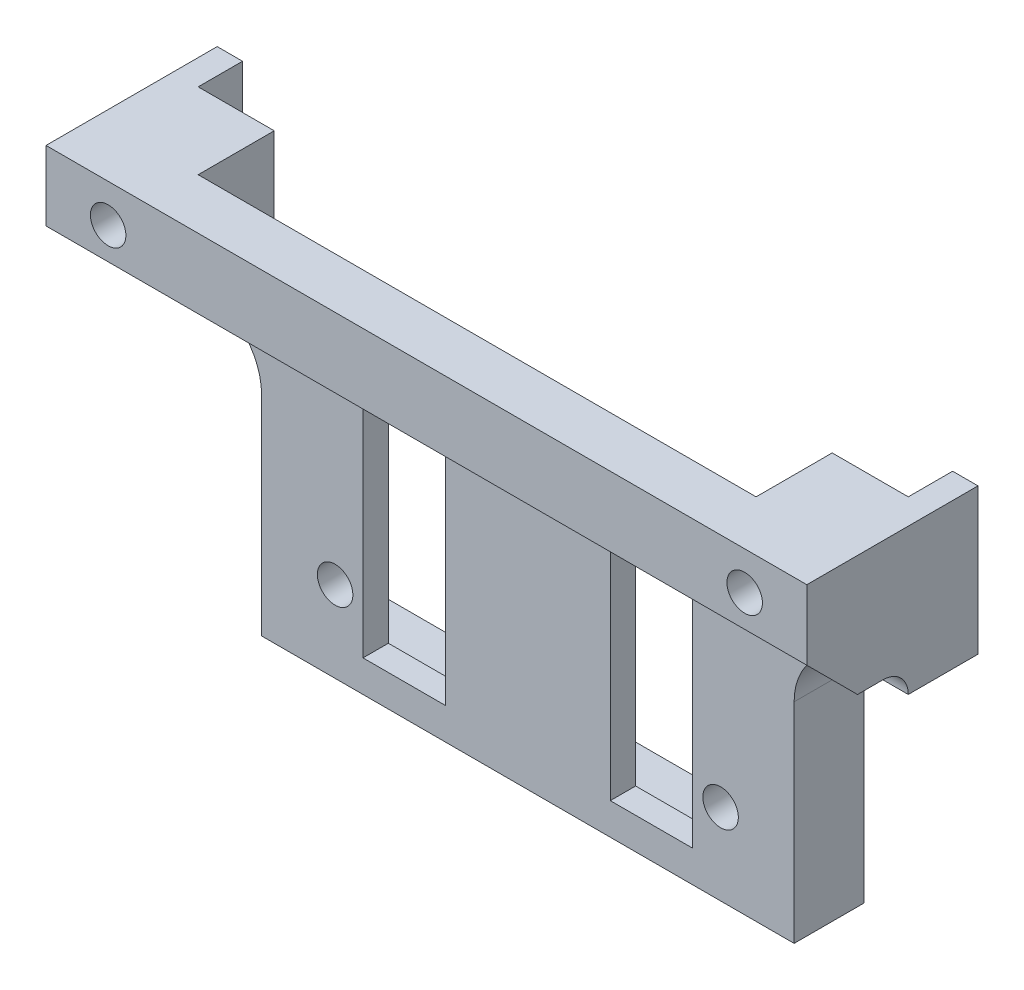
SolidWorks part; units mm, degrees
ref_plane "前视基准面" through (0, 0, 0) normal (0, 0, 1) x (1, 0, 0)
ref_plane "上视基准面" through (0, 0, 0) normal (0, 1, 0) x (1, 0, 0)
ref_plane "右视基准面" through (0, 0, 0) normal (1, 0, 0) x (0, 0, -1)
sketch "草图1" plane through (0, 0, 0) normal (0, 0, 1) x (1, 0, 0)
  line L1 (-21, 17.5) -> (21, 17.5)
  line L2 (-21, 17.5) -> (-21, -17.5)
  line L3 (-21, -17.5) -> (21, -17.5)
  line L4 (21, 17.5) -> (21, -17.5)
  line L5 (0, -17.5) -> (0, 17.5) construction
  line L6 (-21, 0) -> (21, 0) construction
  point P0 (0, 0)
  dimension "D1" = 35
  dimension "D2" = 42
extrude "凸台-拉伸1" add sketch "草图1" along normal blind 10
sketch "草图2" plane through (0, 0, 10) normal (0, 0, 1) x (1, 0, 0)
  line L0 (0, 11.512) -> (0, -11.1488) construction
  line L1 (-21, -17.5) -> (21, -17.5) construction
  line L2 (-13, 8) -> (-6.5, 8)
  line L3 (-13, 8) -> (-13, -13)
  line L4 (-13, -13) -> (-6.5, -13)
  line L5 (-6.5, 8) -> (-6.5, -13)
  line L6 (6.5, 8) -> (6.5, -13)
  line L7 (13, -13) -> (6.5, -13)
  line L8 (13, 8) -> (13, -13)
  line L9 (13, 8) -> (6.5, 8)
  dimension "D1" = 13
  dimension "D2" = 26
  dimension "D3" = 4.5
  dimension "D4" = 21
extrude "切除-拉伸1" cut sketch "草图2" against normal blind 10
sketch "草图5" plane through (0, 0, 0) normal (0, 0, -1) x (-1, 0, 0)
  line L0 (-21, 17.5) -> (21, 17.5) construction
  line L1 (-21, 17.5) -> (-30, 17.5)
  line L2 (-21, 17.5) -> (-21, 6)
  line L3 (-21, 6) -> (-30, 6)
  line L4 (-30, 17.5) -> (-30, 6)
  line L5 (-21, -17.5) -> (-21, 17.5) construction
  line L6 (0, 25.3012) -> (0, -3.3354) construction
  line L7 (30, 17.5) -> (30, 6)
  line L8 (21, 6) -> (30, 6)
  line L9 (21, 17.5) -> (21, 6)
  line L10 (21, 17.5) -> (30, 17.5)
  dimension "D1" = 11.5
  dimension "D2" = 9
extrude "凸台-拉伸2" add sketch "草图5" against normal up to surface (10 mm away) up to face at (9.75, -2.5, 10)
sketch "草图6" plane through (0, 0, 0) normal (0, 0, -1) x (-1, 0, 0)
  circle A0 centre (-25.1, 14.5) radius 1.4 construction
  circle A1 centre (25.1, 14.5) radius 1.4 construction
  circle A2 centre (-25.1, 14.5) radius 1.4
  circle A3 centre (25.1, 14.5) radius 1.4
  circle A4 centre (15.2, -9.1) radius 1.4 construction
  circle A5 centre (-15.2, -9.1) radius 1.4 construction
  circle A6 centre (-15.2, -9.1) radius 1.4
  circle A7 centre (15.2, -9.1) radius 1.4
extrude "切除-拉伸4" cut sketch "草图6" against normal blind 10
sketch "草图3" plane through (0, 0, 0) normal (0, 0, -1) x (-1, 0, 0)
  line L1 (-30, 17.5) -> (30, 17.5) construction
  line L2 (22, 9.5) -> (-22, 9.5)
  line L3 (22, 9.5) -> (22, 17.5)
  line L4 (22, 17.5) -> (-22, 17.5)
  line L5 (-22, 9.5) -> (-22, 17.5)
  line L6 (0, 17.5) -> (0, 9.5) construction
  line L7 (22, 13.5) -> (-22, 13.5) construction
  point P0 (0, 13.5)
  dimension "D1" = 44
  dimension "D2" = 8
extrude "切除-拉伸2" cut sketch "草图3" against normal blind 6
sketch "草图8" plane through (0, 0, 10) normal (0, 0, 1) x (1, 0, 0)
  line L0 (-26.679, -15.5) -> (32.738, -15.5)
  line L1 (-21, -17.5) -> (21, -17.5) construction
  dimension "D1" = 2
extrude "切除-拉伸-薄壁1" cut sketch "草图8" against normal blind 10 and the other way through all thin
sketch "草图10" plane through (0, 0, 0) normal (0, 0, -1) x (-1, 0, 0)
  line L0 (-30, 17.5) -> (-28, 17.5)
  line L1 (-30, 17.5) -> (-22, 17.5) construction
  line L2 (-28, 17.5) -> (-28, 7)
  line L3 (-28, 7) -> (-19, 7)
  line L4 (-19, 7) -> (-19, -13.5)
  line L5 (-19, -13.5) -> (19, -13.5)
  line L6 (0, 4.8955) -> (0, -18.7545) construction
  line L7 (30, 6) -> (21, 6)
  line L8 (30, 17.5) -> (30, 6)
  line L9 (21, 6) -> (21, -15.5)
  line L10 (19, 7) -> (19, -13.5)
  line L11 (28, 7) -> (19, 7)
  line L12 (-21, 6) -> (-21, -15.5)
  line L13 (-21, -15.5) -> (21, -15.5)
  line L14 (21, -15.5) -> (21, 6)
  line L15 (21, 6) -> (30, 6)
  line L16 (30, 6) -> (30, 17.5)
  line L17 (30, 17.5) -> (22, 17.5)
  line L18 (22, 17.5) -> (22, 9.5)
  line L19 (22, 9.5) -> (-22, 9.5)
  line L20 (-22, 9.5) -> (-22, 17.5)
  line L21 (-22, 17.5) -> (-30, 17.5)
  line L22 (-30, 17.5) -> (-30, 6)
  line L23 (-30, 6) -> (-21, 6)
  line L24 (-21, 6) -> (-21, -15.5)
  line L25 (-21, -15.5) -> (21, -15.5)
  line L26 (21, -15.5) -> (21, 6)
  line L27 (21, 6) -> (30, 6)
  line L28 (30, 6) -> (30, 17.5)
  line L29 (28, 17.5) -> (28, 7)
  line L30 (30, 17.5) -> (28, 17.5)
  line L34 (-30, 17.5) -> (-30, 6)
  line L35 (-30, 6) -> (-21, 6)
  point P22 (-25.5, 6)
  point P24 (0, -13.5)
  line M26 (-21, 6) -> (-21, -15.5)
  line M27 (-21, -15.5) -> (21, -15.5)
  line M28 (21, -15.5) -> (21, 6)
  line M29 (21, 6) -> (30, 6)
  line M30 (30, 6) -> (30, 17.5)
  line M31 (30, 17.5) -> (22, 17.5)
  line M35 (-22, 17.5) -> (-30, 17.5)
  line M36 (-30, 17.5) -> (-30, 6)
  line M37 (-30, 6) -> (-21, 6)
  dimension "D2" = 2
  dimension "D3" = 2
  dimension "D4" = 1
  dimension "D5" = 2
  dimension "D1" = 0
extrude "凸台-拉伸3" add sketch "草图10" along normal blind 3.5 contours L6 L5 L4 L3 L2 M35 M36 M37 M26 M27 | L5 L6 L25 L29 L11 L10 M28 M29 M30 M31
sketch "草图11" plane through (0, 0, 10) normal (0, 0, 1) x (1, 0, 0)
  circle A0 centre (25.1, 14.5) radius 1.4 construction
  circle A1 centre (-25.1, 14.5) radius 1.4 construction
  circle A2 centre (-15.2, -9.1) radius 1.4 construction
  circle A3 centre (25.1, 14.5) radius 1.4
  circle A4 centre (-25.1, 14.5) radius 1.4
  circle A5 centre (-15.2, -9.1) radius 1.4
  circle A6 centre (-25.1, 14.5) radius 1
  circle A7 centre (25.1, 14.5) radius 1
  circle A8 centre (15.2, -9.1) radius 1
  circle A9 centre (-15.2, -9.1) radius 1
  circle A10 centre (15.2, -9.1) radius 1.4 construction
  circle A11 centre (15.2, -9.1) radius 1.4
  dimension "D1" = 2
  dimension "D2" = 2
  dimension "D3" = 2
  dimension "D4" = 2
extrude "凸台-拉伸4" [suppressed] add sketch "草图11" against normal up to surface (10 mm away)
sketch "草图12" plane through (0, 0, 10) normal (0, 0, 1) x (1, 0, 0)
  line L1 (-30, -15.5) -> (30, -15.5)
  line L2 (-30, -15.5) -> (-30, 8)
  line L3 (-30, 8) -> (30, 8)
  line L4 (30, -15.5) -> (30, 8)
  line L5 (-30, 6) -> (-30, 17.5) construction
  line L6 (30, 17.5) -> (30, 6) construction
  line L7 (21, -15.5) -> (-21, -15.5) construction
  dimension "D1" = 23.5
extrude "切除-拉伸5" cut sketch "草图12" against normal blind 8
fillet "圆角1" radius 5 2 edges at (-21, 6, -0.75) (21, 6, -0.75)
fillet "圆角3" radius 2 3 edges at (21.5, 8, 2) (-21.5, 8, 2) (0, 8, 2)
chamfer "倒角1" distance 4 angle 45 1 edges at (0, 8, 10)
sketch "草图13" plane through (0, 0, -3.5) normal (0, 0, -1) x (-1, 0, 0)
  line L0 (21, -15.5) -> (21, 1) construction
  line L1 (-21, -15.5) -> (21, -15.5)
  line L2 (-21, -15.5) -> (-21, -13.5)
  line L3 (-21, -13.5) -> (21, -13.5)
  line L4 (21, -15.5) -> (21, -13.5)
  line L5 (-19, -13.5) -> (19, -13.5) construction
